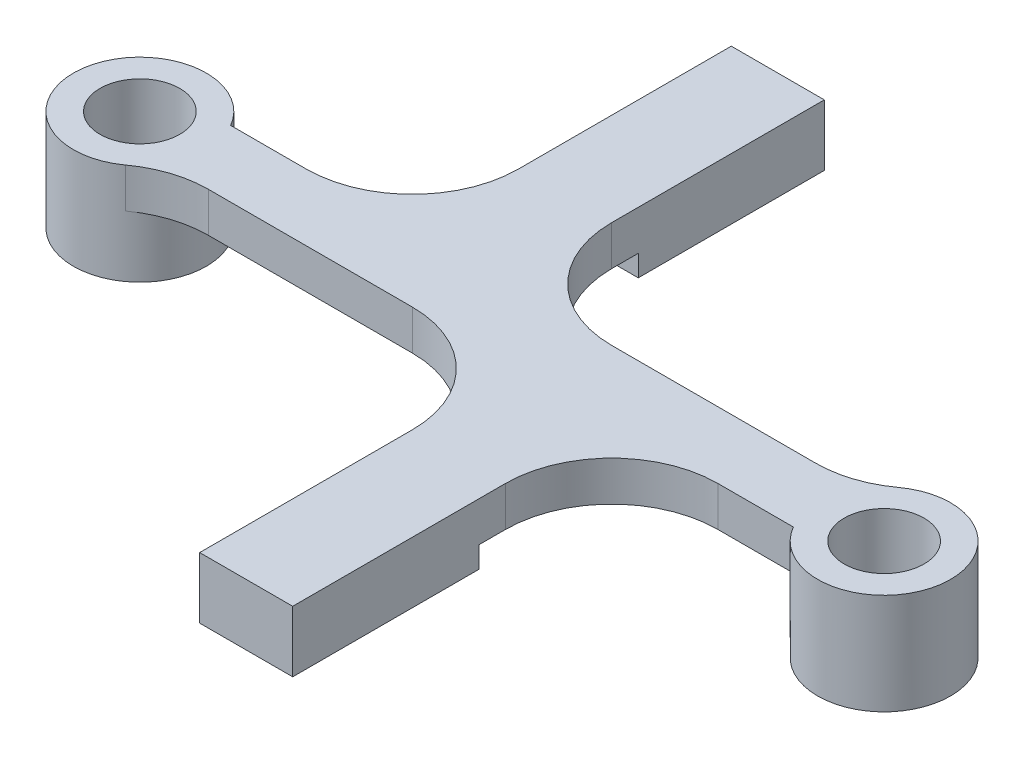
SolidWorks part; units mm, degrees
material "6061-T6 (SS)"
ref_plane "Front Plane" through (0, 0, 0) normal (0, 0, 1) x (1, 0, 0)
ref_plane "Top Plane" through (0, 0, 0) normal (0, 1, 0) x (1, 0, 0)
ref_plane "Right Plane" through (0, 0, 0) normal (1, 0, 0) x (0, 0, -1)
sketch "Sketch1" plane through (0, 0, 0) normal (0, 1, 0) x (1, 0, 0)
  line L0 (-14, 0) -> (14, 0) construction
  line L1 (0, 1.25) -> (0, 0) construction
  line L2 (-11.8349, 1.25) -> (11.8349, 1.25)
  line L3 (-11.8349, 1.25) -> (-11.8349, -1.25)
  line L4 (-11.8349, -1.25) -> (11.8349, -1.25)
  line L5 (11.8349, 1.25) -> (11.8349, -1.25)
  circle A0 centre (-14, 0) radius 1.5
  circle A1 centre (14, 0) radius 1.5
  circle A2 centre (-14, 0) radius 2.5
  circle A3 centre (14, 0) radius 2.5
  point P24 (-11.8349, 0)
  dimension "D2" = 2.5
  dimension "D3" = 5
  dimension "D4" = 3
  dimension "D1" = 28
extrude "Boss-Extrude2" add sketch "Sketch1" along normal blind 3.8 contours L3 A2 A0 | L3 A2 | A3 L2 A2 L4 | L5 A3 | L5 A3 A1
sketch "Sketch2" plane through (0, 3.8, 0) normal (0, 1, 0) x (1, 0, 0)
  line L0 (-11.8349, 1.25) -> (11.8349, 1.25) construction
  line L1 (-5, 6.25) -> (-1.5, 6.25)
  line L2 (-5, 6.25) -> (-5, 13.25)
  line L3 (-5, 13.25) -> (-1.5, 13.25)
  line L4 (-1.5, 6.25) -> (-1.5, 13.25)
  line L5 (-5, 6.25) -> (-1.5, 6.25)
  line L6 (-5, 6.25) -> (-5, 1.25)
  line L7 (-5, 1.25) -> (-1.5, 1.25)
  line L8 (-1.5, 6.25) -> (-1.5, 1.25)
  line L9 (-11.8349, -1.25) -> (11.8349, -1.25) construction
  line L10 (1.5, -1.25) -> (5, -1.25)
  line L11 (1.5, -1.25) -> (1.5, -6.25)
  line L12 (1.5, -6.25) -> (5, -6.25)
  line L13 (5, -1.25) -> (5, -6.25)
  line L14 (3.25, -13.25) -> (3.25, 2.053) construction
  line L15 (1.5, -6.25) -> (5, -6.25)
  line L16 (1.5, -6.25) -> (1.5, -13.25)
  line L17 (1.5, -13.25) -> (5, -13.25)
  line L18 (5, -6.25) -> (5, -13.25)
  line L19 (0, 0) -> (0, -20.7771) construction
  line L20 (-3.25, 13.25) -> (-3.25, -0.5729) construction
  line L21 (-1.5, 9.75) -> (-5, 9.75) construction
  line L22 (0, 0) -> (-14, 0) construction
  line L23 (5, -9.75) -> (1.5, -9.75) construction
  arc M7 (-11.8349, 1.25) -> (-11.8349, -1.25) centre (-14, 0) ccw
  line M10 (11.8349, 1.25) -> (-11.8349, 1.25)
  dimension "D1" = 7
  dimension "D3" = 3.25
  dimension "D4" = 9.75
  dimension "D5" = 7
  dimension "D6" = 3.5
  dimension "D2" = 3.5
  dimension "D7" = 3.25
  dimension "D8" = 9.75
extrude "Boss-Extrude3" add sketch "Sketch2" against normal up to surface (3.8 mm away) contours L1 L4 L3 L2 | L8 L1 L6 M7 M10 | L11 L10 L13 L12 | L16 L15 L18 L17 up to face at (-14, 0, 1.5)
sketch "Sketch3" plane through (0, 0, 0) normal (0, -1, 0) x (1, 0, 0)
  line L0 (1.5, 6.25) -> (5, 6.25) construction
  line L1 (5, 1.25) -> (5, 6.25) construction
  line L2 (1.5, 1.25) -> (5, 1.25) construction
  line L3 (1.5, 1.25) -> (1.5, 6.25) construction
  line L4 (1.5, 6.25) -> (5, 6.25) construction
  line L5 (1.5, 6.25) -> (1.5, 13.25) construction
  line L6 (1.5, 13.25) -> (5, 13.25) construction
  line L7 (5, 6.25) -> (5, 13.25) construction
  line L8 (-5, -6.25) -> (-1.5, -6.25) construction
  line L9 (-5, -6.25) -> (-5, -13.25) construction
  line L10 (-5, -13.25) -> (-1.5, -13.25) construction
  line L11 (-1.5, -6.25) -> (-1.5, -13.25) construction
  line L12 (-5, -6.25) -> (-1.5, -6.25) construction
  line L13 (-5, -6.25) -> (-5, -1.25) construction
  line L14 (-5, -1.25) -> (-1.5, -1.25) construction
  line L15 (-1.5, -6.25) -> (-1.5, -1.25) construction
  line L16 (1.5, 6.25) -> (5, 6.25)
  line L17 (5, 1.25) -> (5, 6.25)
  line L18 (1.5, 1.25) -> (5, 1.25)
  line L19 (1.5, 1.25) -> (1.5, 6.25)
  line L20 (1.5, 6.25) -> (5, 6.25)
  line L21 (1.5, 6.25) -> (1.5, 13.25)
  line L22 (1.5, 13.25) -> (5, 13.25)
  line L23 (5, 6.25) -> (5, 13.25)
  line L24 (-5, -6.25) -> (-1.5, -6.25)
  line L25 (-5, -6.25) -> (-5, -13.25)
  line L26 (-5, -13.25) -> (-1.5, -13.25)
  line L27 (-1.5, -6.25) -> (-1.5, -13.25)
  line L28 (-5, -6.25) -> (-1.5, -6.25)
  line L29 (-5, -6.25) -> (-5, -1.25)
  line L30 (-5, -1.25) -> (-1.5, -1.25)
  line L31 (-1.5, -6.25) -> (-1.5, -1.25)
  line L32 (-1.5, -1.25) -> (11.8349, -1.25)
  line L33 (1.5, 1.25) -> (-11.8349, 1.25)
  circle A0 centre (14, 0) radius 2.5
  circle A1 centre (-14, 0) radius 2.5
  line M3 (5, 1.25) -> (5, 13.25)
  line M5 (1.5, 13.25) -> (1.5, 1.25)
  line M6 (1.5, 1.25) -> (-11.8349, 1.25)
  line M8 (-5, -1.25) -> (-5, -13.25)
  line M10 (-1.5, -13.25) -> (-1.5, -1.25)
  line M11 (-1.5, -1.25) -> (11.8349, -1.25)
extrude "Cut-Extrude1" cut sketch "Sketch3" against normal offset from surface (2.3 mm away) 1.5 contours A1 L30 A0 L18 M11 M6 | A0 L16 L18 M3 M5 | A1 L24 L30 M8 M10
sketch "Sketch4" plane through (0, 0, 0) normal (0, -1, 0) x (1, 0, 0)
  line L0 (-1.5, -13.25) -> (-1.5, -6.25) construction
  line L1 (-1.5, -6.25) -> (-5, -6.25) construction
  line L2 (-5, -6.25) -> (-5, -13.25) construction
  line L3 (-5, -13.25) -> (-1.5, -13.25) construction
  line L4 (1.5, 6.25) -> (5, 6.25) construction
  line L5 (5, 6.25) -> (5, 13.25) construction
  line L6 (5, 13.25) -> (1.5, 13.25) construction
  line L7 (1.5, 13.25) -> (1.5, 6.25) construction
  line L8 (-1.5, -13.25) -> (-1.5, -6.25)
  line L9 (-1.5, -6.25) -> (-5, -6.25)
  line L10 (-5, -6.25) -> (-5, -13.25)
  line L11 (-5, -13.25) -> (-1.5, -13.25)
  line L12 (1.5, 6.25) -> (5, 6.25)
  line L13 (5, 6.25) -> (5, 13.25)
  line L14 (5, 13.25) -> (1.5, 13.25)
  line L15 (1.5, 13.25) -> (1.5, 6.25)
extrude "Cut-Extrude2" cut sketch "Sketch4" against normal blind 1.5
fillet "Fillet1" radius 4 6 edges at (-1.5, 3.05, -1.25) (-11.8349, 3.05, 1.25) (1.5, 3.05, 1.25) (11.8349, 3.05, -1.25) (-5, 3.05, -1.25) (5, 3.05, 1.25)
